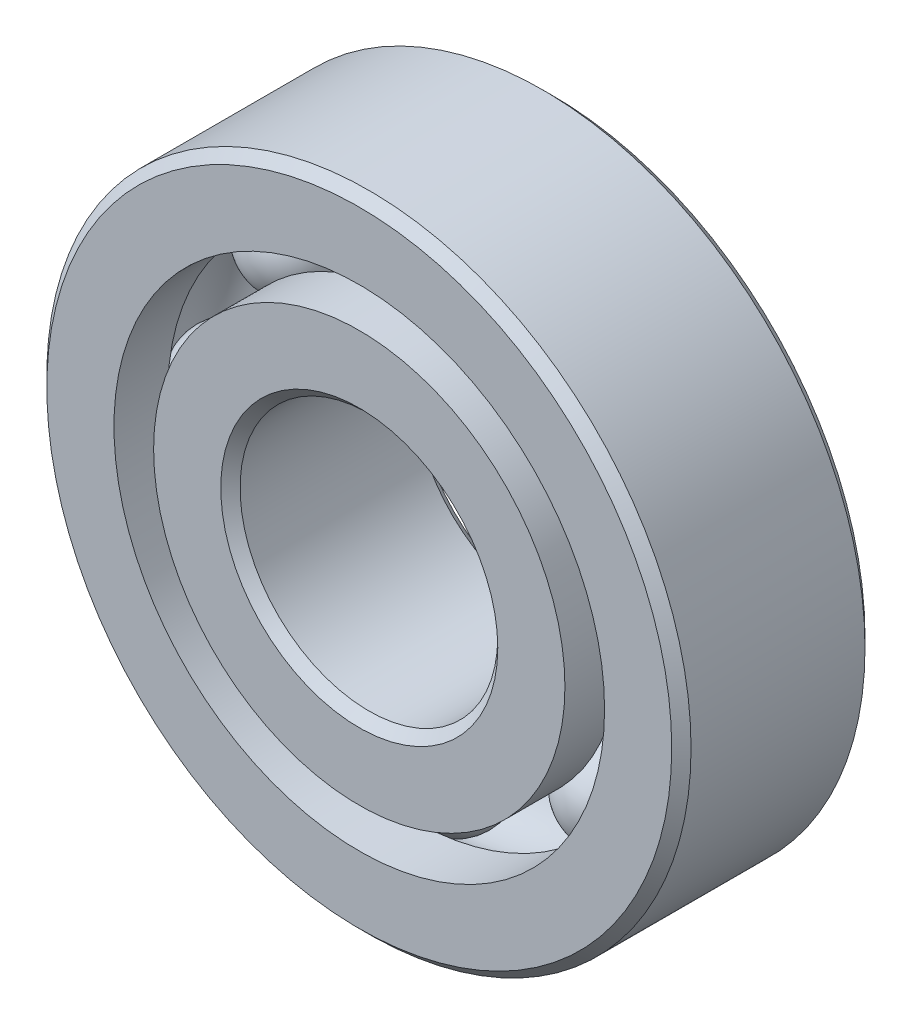
SolidWorks part; units mm, degrees
ref_plane "Front Plane" through (0, 0, 0) normal (0, 0, 1) x (1, 0, 0)
ref_plane "Top Plane" through (0, 0, 0) normal (0, 1, 0) x (1, 0, 0)
ref_plane "Right Plane" through (0, 0, 0) normal (1, 0, 0) x (0, 0, -1)
sketch "Sketch1" plane through (0, 0, 0) normal (1, 0, 0) x (0, 0, -1)
  line L0 (-2.3812, 0) -> (2.3812, 0) construction
  line L1 (0, 7.9375) -> (0, -7.9375) construction
  line L2 (2.1431, 7.9375) -> (-2.1431, 7.9375)
  line L3 (-2.1431, 7.9375) -> (-2.3813, 7.6994)
  line L4 (-2.3813, 7.6994) -> (-2.3813, 6.0447)
  line L5 (-2.3813, 6.0447) -> (-1.0583, 6.0447)
  line L6 (2.3813, 6.0447) -> (1.0583, 6.0447)
  line L7 (2.3813, 7.6994) -> (2.3813, 6.0447)
  line L8 (2.1431, 7.9375) -> (2.3813, 7.6994)
  line L9 (0, 7.9375) -> (0, 5.5562) construction
  line L10 (0, 5.5562) -> (0, 3.175) construction
  arc A0 (-1.0583, 6.0447) -> (1.0583, 6.0447) centre (0, 5.5562) cw
  point P14 (0, 3.175)
  dimension "D3" = 2.1167
  dimension "D1" = 45
  dimension "Width" = 4.7625
  dimension "OD" = 15.875
  dimension "D2" = 0.2381
  dimension "Shaft Dia" = 6.35
  dimension "D4" = 0.4885
revolve "Revolve1" add sketch "Sketch1" angle 360 about L0
sketch "Sketch3" plane through (0, 0, 0) normal (1, 0, 0) x (0, 0, -1)
  line L0 (-2.3813, 5.0678) -> (-1.0583, 5.0678)
  line L1 (0, 7.9375) -> (0, -7.9375) construction
  line L2 (-2.3813, 7.6994) -> (-2.3813, 6.0447) construction
  line L3 (-2.3813, 5.0678) -> (-2.3813, 3.4131)
  line L4 (-2.1431, 7.9375) -> (-2.3813, 7.6994) construction
  line L5 (-2.3813, 3.4131) -> (-2.1431, 3.175)
  line L6 (-2.1431, 3.175) -> (2.1431, 3.175)
  line L7 (2.1431, 7.9375) -> (2.1431, -7.9375) construction
  line L8 (2.1431, 3.175) -> (2.3813, 3.4131)
  line L9 (2.3813, -7.6994) -> (2.3813, 7.6994) construction
  line L10 (2.3813, 3.4131) -> (2.3813, 5.0678)
  line L11 (2.3813, 5.0678) -> (1.0583, 5.0678)
  line L13 (2.1431, 7.9375) -> (2.3813, 7.6994) construction
  arc A0 (1.0583, 6.0447) -> (-1.0583, 6.0447) centre (0, 5.5562) ccw construction
  arc A1 (1.0583, 5.0678) -> (-1.0583, 5.0678) centre (0, 5.5562) cw
revolve "Revolve3" add sketch "Sketch3" angle 360 about L0
sketch "Sketch4" plane through (0, 0, 0) normal (1, 0, 0) x (0, 0, -1)
  line L0 (-1.1656, 5.5562) -> (1.1656, 5.5562)
  arc A2 (-1.1656, 5.5562) -> (1.1656, 5.5562) centre (0, 5.5562) cw
  arc A3 (1.0583, 6.0447) -> (-1.0583, 6.0447) centre (0, 5.5562) ccw construction
revolve "Revolve4" add sketch "Sketch4" angle 360 about L0
ref_axis "Axis1" through (0, 0, -2.3812) along (0, 0, 1)
pattern_circular "CirPattern1" count 8 every 45 about axis through (0, 0, -2.3812) along (0, 0, 1) of bodies 104
sketch "Sketch5" plane through (0, 0, 0) normal (1, 0, 0) x (0, 0, -1)
  line L0 (-2.3813, 6.0447) -> (-1.0583, 6.0447) construction
  line L1 (-2.2622, 6.0447) -> (-1.1656, 6.0447)
  line L2 (-2.2622, 6.0447) -> (-2.2622, 5.0678)
  line L3 (-2.2622, 5.0678) -> (-1.1656, 5.0678)
  line L4 (-1.1656, 6.0447) -> (-1.1656, 5.0678)
  line L5 (-2.3813, 5.0678) -> (-1.0583, 5.0678) construction
  line L6 (2.3813, 6.0447) -> (1.0583, 6.0447) construction
  line L7 (2.2622, 6.0447) -> (1.1656, 6.0447)
  line L8 (2.2622, 6.0447) -> (2.2622, 5.0678)
  line L9 (2.2622, 5.0678) -> (1.1656, 5.0678)
  line L10 (1.1656, 6.0447) -> (1.1656, 5.0678)
  line L11 (2.3813, 5.0678) -> (1.0583, 5.0678) construction
  line L12 (-2.1431, 7.9375) -> (-2.3813, 7.6994) construction
  point P18 (-2.2622, 7.8184)
revolve "Revolve5" [suppressed] add sketch "Sketch5" angle 360 about L0
equation "\"D2@Sketch1\" = \"Width@Sketch1\"*.05"
equation "\"D3@Sketch1\" = \"Width@Sketch1\"/2.25"
equation "\"D4@Sketch1\" = (((\"OD@Sketch1\"-\"Width@Sketch1\")/2)/3.25)/3.5"
equation "\"D2@CirPattern1\" = 360/\"Balls@CirPattern1\""
